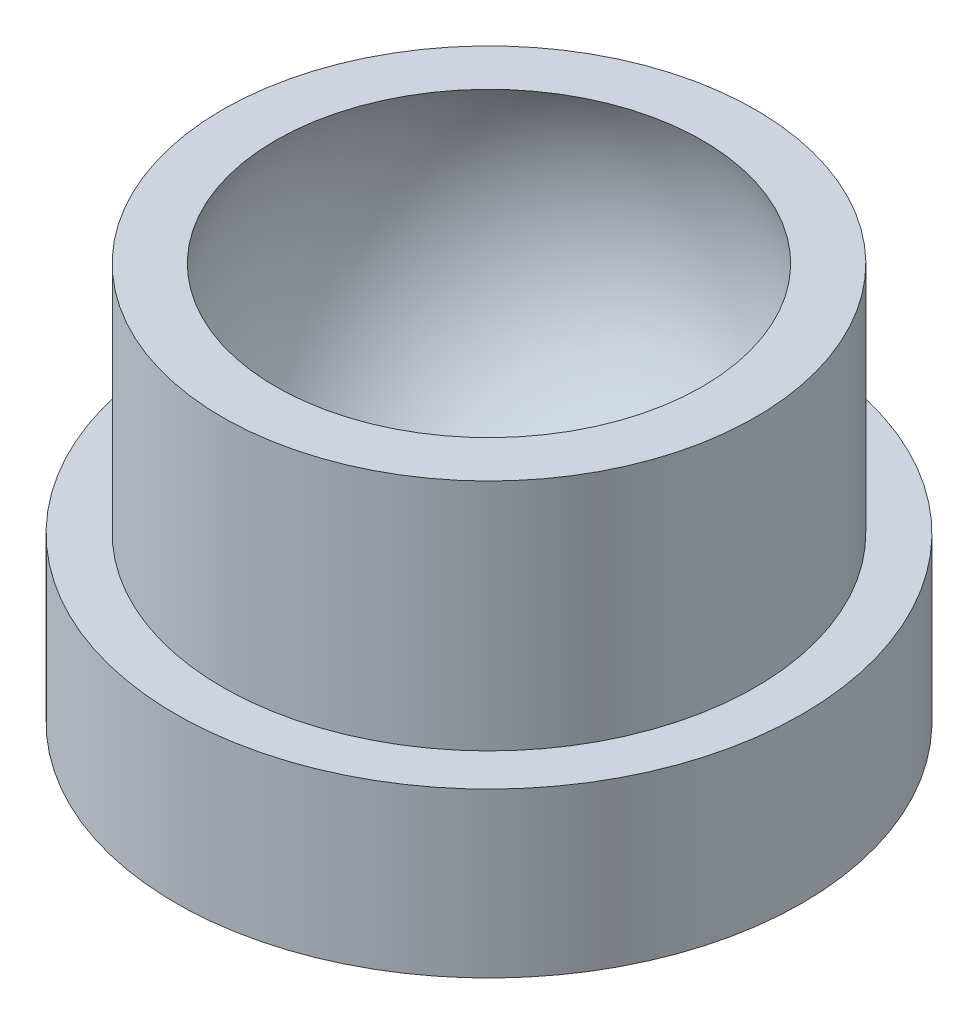
SolidWorks part; units mm, degrees
material "ABS"
ref_plane "Front Plane" through (0, 0, 0) normal (0, 0, 1) x (1, 0, 0)
ref_plane "Top Plane" through (0, 0, 0) normal (0, 1, 0) x (1, 0, 0)
ref_plane "Right Plane" through (0, 0, 0) normal (1, 0, 0) x (0, 0, -1)
sketch "Sketch1" plane through (0, 0, 0) normal (0, 0, 1) x (1, 0, 0)
  line L0 (0, 0) -> (2.54, 0)
  line L1 (34.036, 0) -> (34.036, -8.89)
  line L2 (34.036, -8.89) -> (0, -8.89)
  line L3 (0, -8.89) -> (0, 0)
  line L4 (2.54, 0) -> (2.54, 12.7)
  line L5 (2.54, 12.7) -> (31.496, 12.7)
  line L6 (31.496, 12.7) -> (31.496, 0)
  line L7 (31.496, 0) -> (34.036, 0)
  line L8 (17.018, 12.7) -> (17.018, -8.89)
  point P7 (17.018, 12.7)
  point P11 (17.018, -8.89)
  dimension "D1" = 34.036
  dimension "D2" = 8.89
  dimension "D3" = 12.7
  dimension "D4" = 28.956
revolve "Revolve1" add sketch "Sketch1" angle 360 about L8 region at (24.8303, 1.4772, 0)
sketch "Sketch2" plane through (0, 0, 0) normal (0, 0, 1) x (1, 0, 0)
  line L2 (4.318, 7.5108) -> (29.718, 7.5108)
  line L3 (31.496, 12.7) -> (2.54, 12.7) construction
  arc A0 (29.718, 7.5108) -> (4.318, 7.5108) centre (17.018, 7.5108) ccw
  point P5 (16.4051, 7.5108)
  dimension "D1" = 25.4
  dimension "D2" = 5.1892
  dimension "D3" = 14.478
revolve "Cut-Revolve1" cut sketch "Sketch2" angle 360 about L2
